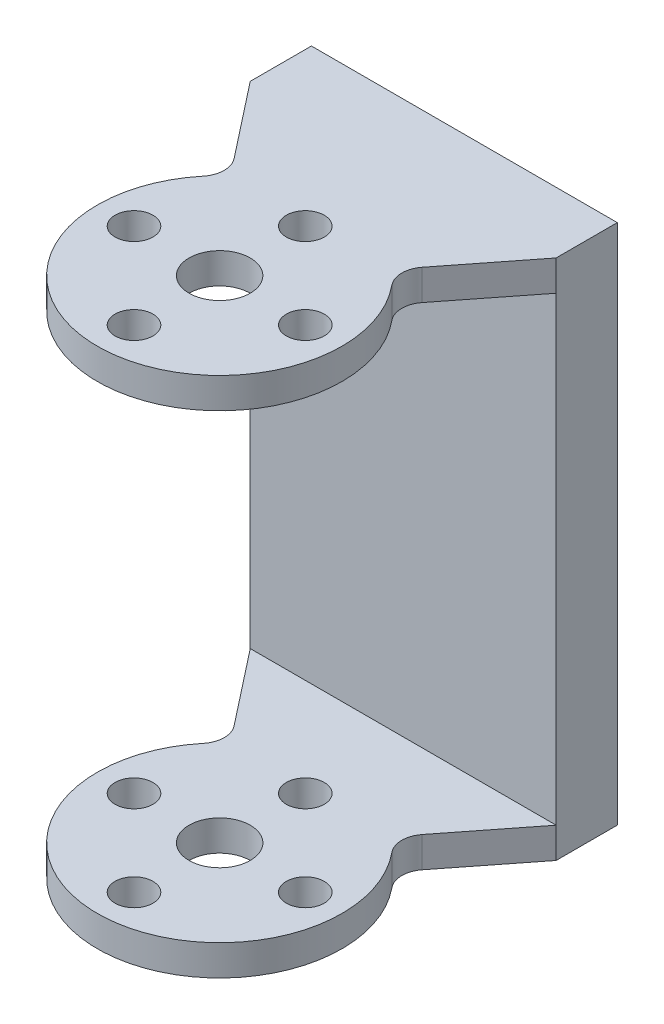
SolidWorks part; units mm, degrees
ref_plane "Front Plane" through (0, 0, 0) normal (0, 0, 1) x (1, 0, 0)
ref_plane "Top Plane" through (0, 0, 0) normal (0, 1, 0) x (1, 0, 0)
ref_plane "Right Plane" through (0, 0, 0) normal (1, 0, 0) x (0, 0, -1)
sketch "Sketch1" plane through (0, 0, 0) normal (0, 1, 0) x (1, 0, 0)
  line L2 (-12.5, 15) -> (-12.5, 20)
  line L3 (-12.5, 20) -> (12.5, 20)
  line L4 (12.5, 15) -> (12.5, 20)
  line L5 (-12.5, 15) -> (-6.6144, 7.5)
  line L6 (6.6144, 7.5) -> (12.5, 15)
  circle A3 centre (0, 0) radius 2.5
  arc A4 (-6.6144, 7.5) -> (6.6144, 7.5) centre (0, 0) ccw
  point P0 (6.7591, 7.3698)
  point P12 (-12.5, 0)
  point P13 (0, 20)
  dimension "D3" = 0
  dimension "D4" = 20
  dimension "D6" = 5
  dimension "D2" = 10
  dimension "D1" = 25
  dimension "D5" = 5
  dimension "D7" = 12.5
extrude "Boss-Extrude1" add sketch "Sketch1" along normal blind 42.65
sketch "Sketch2" plane through (-12.5, 0, 0) normal (-1, 0, 0) x (0, 0, 1)
  line L1 (25, 2.5) -> (-15, 2.5)
  line L2 (25, 2.5) -> (25, 40.15)
  line L3 (25, 40.15) -> (-15, 40.15)
  line L4 (-15, 2.5) -> (-15, 40.15)
  line L5 (-20, 42.65) -> (-20, 0) construction
  point P6 (-20, 21.325)
  point P7 (25, 21.325)
  dimension "D1" = 37.65
  dimension "D2" = 5
  dimension "D3" = 45
extrude "Cut-Extrude1" cut sketch "Sketch2" against normal through all
ref_plane "B mid plane" through (0, 21.325, 0) normal (0, -1, 0) x (-1, 0, 0)
sketch "Sketch3" plane through (0, 42.65, 0) normal (0, 1, 0) x (1, 0, 0)
  circle A0 centre (0, 7) radius 1.55
  circle A1 centre (0, 0) radius 2.5 construction
  dimension "D1" = 3.1
  dimension "D2" = 7
  dimension "D3" = 0
extrude "Cut-Extrude2" cut sketch "Sketch3" against normal through all
ref_axis "Axis1" through (0, 42.65, 0) along (0, -1, 0)
pattern_circular "CirPattern1" count 4 over 360 about axis through (0, 42.65, 0) along (0, -1, 0) of "Cut-Extrude2"
fillet "Fillet1" radius 2 4 edges at (6.6144, 41.4, -7.5) (6.6144, 1.25, -7.5) (-6.6144, 41.4, -7.5) (-6.6144, 1.25, -7.5)
